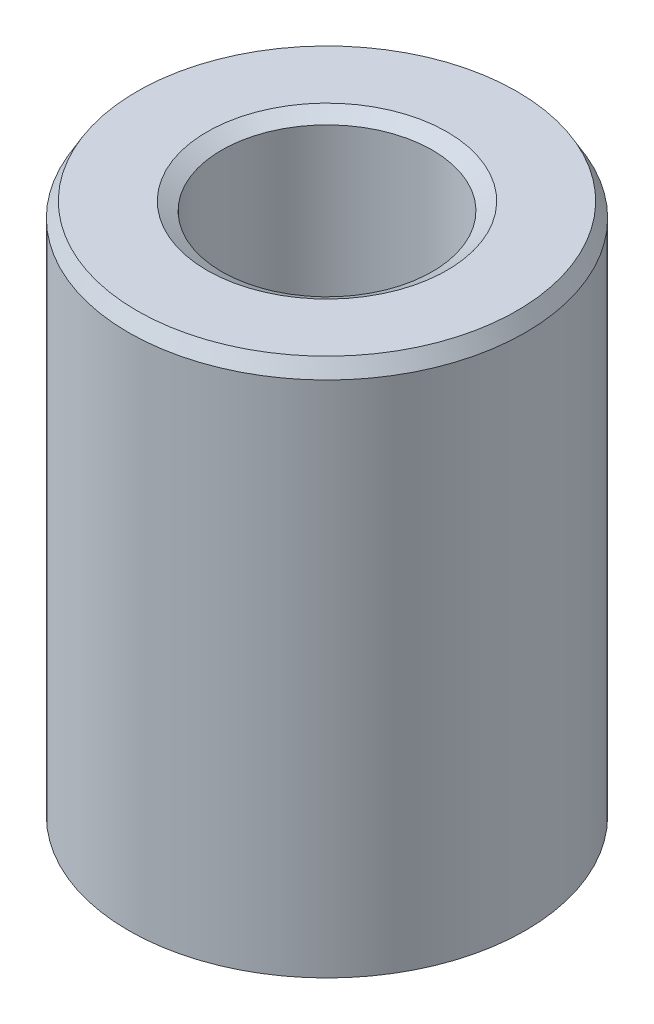
SolidWorks part; units mm, degrees
ref_plane "Front Plane" through (0, 0, 0) normal (0, 0, 1) x (1, 0, 0)
ref_plane "Top Plane" through (0, 0, 0) normal (0, 1, 0) x (1, 0, 0)
ref_plane "Right Plane" through (0, 0, 0) normal (1, 0, 0) x (0, 0, -1)
sketch "Sketch1" plane through (0, 0, 0) normal (0, 1, 0) x (1, 0, 0)
  circle A0 centre (0, 0) radius 7.5
  dimension "SLEEVE_OD" = 15
extrude "Boss-Extrude1" add sketch "Sketch1" along normal blind 20.4448
sketch "Sketch2" plane through (0, 0, 0) normal (0, 1, 0) x (1, 0, 0)
  circle A0 centre (0, 0) radius 3.9813
  dimension "BORE_D" = 7.9626
extrude "Cut-Extrude1" cut sketch "Sketch2" along normal through all
chamfer "Chamfer1" distance 0.5541 angle 30 4 edges at (0, 20.4448, 3.9813) (0, 0, 3.9813) (0, 0, 7.5) (0, 20.4448, 7.5) first distance on face at (0, 20.4448, 3.9813) first distance on face at (0, 0, 3.9813) first distance on face at (0, 20.4448, 7.5)
